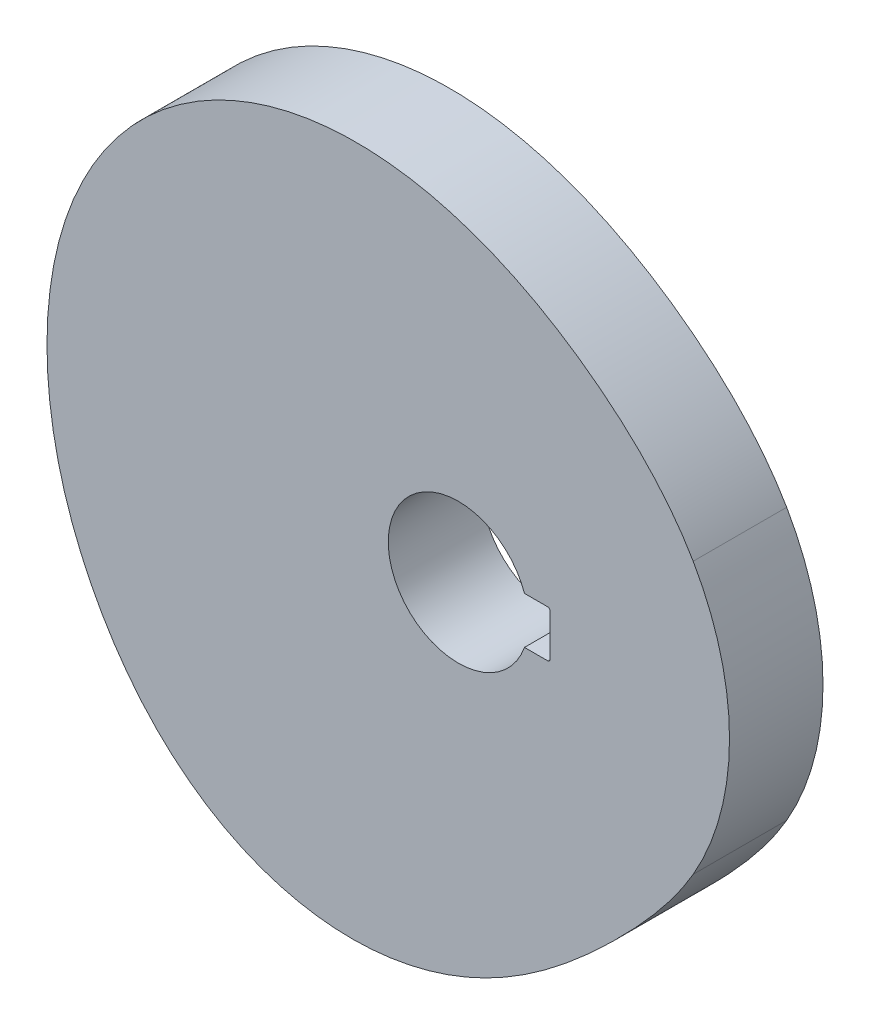
SolidWorks part; units mm, degrees
material "Plain Carbon Steel"
ref_plane "Front Plane" through (0, 0, 0) normal (0, 0, 1) x (1, 0, 0)
ref_plane "Top Plane" through (0, 0, 0) normal (0, 1, 0) x (1, 0, 0)
ref_plane "Right Plane" through (0, 0, 0) normal (1, 0, 0) x (0, 0, -1)
sketch "Displacement Sketch" plane through (0, 0, 0) normal (0, 0, 1) x (1, 0, 0)
  line L0 (0, 15) -> (0, 0) construction
  line L1 (0, 0) -> (47.1239, 0) construction
  line L2 (3.927, 0) -> (3.927, 15) construction
  line L3 (23.5619, 0) -> (23.5619, 15) construction
  line L4 (27.4889, 0) -> (27.4889, 15) construction
  line L5 (43.1969, 0) -> (43.1969, 15) construction
  line L6 (47.1239, 0) -> (47.1239, 15) construction
  line L7 (0, 0) -> (3.927, 0)
  line L8 (27.4889, 15) -> (23.5619, 15)
  line L9 (43.1969, 0) -> (47.1239, 0)
  spline S0 degree 4 poles (1.962, -0.0967) (2.0251, -0.0879) (2.1497, -0.0715) (2.3802, -0.0441) (2.7786, -0.0172) (3.1491, -0.0023) (3.8234, 0.0011) (4.1519, -0.0013) (4.7825, 0.0037) (5.2973, 0.0292) (5.8993, 0.0828) (6.4992, 0.198) (7.1843, 0.4092) (7.8229, 0.6945) (8.5028, 1.0958) (9.2434, 1.664) (10.1514, 2.5325) (11.1276, 3.6845) (12.1583, 5.0983) (13.2223, 6.6951) (14.2666, 8.3049) (15.3308, 9.9017) (16.361, 11.3155) (17.3382, 12.4675) (18.2447, 13.336) (18.9876, 13.9042) (19.6636, 14.3055) (20.2354, 14.5584) (20.6913, 14.7109) (21.0546, 14.8041) (21.3223, 14.8591) (21.5625, 14.8998) (21.7937, 14.9296) (22.0274, 14.9566) (22.3642, 14.9781) (22.6856, 14.9963) (23.3417, 15.0013) (23.6628, 14.9989) (24.3418, 15.0023) (24.7635, 15.0193) (25.1747, 15.049) (25.3985, 15.0791) (25.5259, 15.0967) knots 0 0 0 0 0 0.008159 0.016318 0.032637 0.048955 0.065274 0.0892 0.101163 0.113126 0.142767 0.163984 0.185201 0.206418 0.236195 0.268021 0.309045 0.372696 0.436348 0.5 0.563652 0.627304 0.690955 0.731979 0.763805 0.793582 0.814799 0.836016 0.846625 0.857233 0.864643 0.872053 0.879463 0.886874 0.898837 0.9108 0.934726 0.951045 0.967363 0.983682 1 1 1 1 1 construction
  spline S1 degree 4 poles (3.927, 0) (4.0838, 0) (4.3123, 0) (4.7825, 0.0037) (5.2973, 0.0292) (5.8993, 0.0828) (6.4992, 0.198) (7.1843, 0.4092) (7.8229, 0.6945) (8.5028, 1.0958) (9.2434, 1.664) (10.1514, 2.5325) (11.1276, 3.6845) (12.1583, 5.0983) (13.2223, 6.6951) (14.2666, 8.3049) (15.3308, 9.9017) (16.361, 11.3155) (17.3382, 12.4675) (18.2447, 13.336) (18.9876, 13.9042) (19.6636, 14.3055) (20.2354, 14.5584) (20.6913, 14.7109) (21.0546, 14.8041) (21.3223, 14.8591) (21.5625, 14.8998) (21.7937, 14.9296) (22.0274, 14.9566) (22.3642, 14.9781) (22.6856, 14.9963) (23.1748, 15) (23.4052, 15) (23.5619, 15) knots 0.065274 0.065274 0.065274 0.065274 0.065274 0.0892 0.101163 0.113126 0.142767 0.163984 0.185201 0.206418 0.236195 0.268021 0.309045 0.372696 0.436348 0.5 0.563652 0.627304 0.690955 0.731979 0.763805 0.793582 0.814799 0.836016 0.846625 0.857233 0.864643 0.872053 0.879463 0.886874 0.898837 0.9108 0.934726 0.934726 0.934726 0.934726 0.934726
  spline S2 degree 4 poles (25.917, 15.0967) (25.9672, 15.0879) (26.0664, 15.0716) (26.2503, 15.0442) (26.5692, 15.0173) (26.8684, 15.0023) (27.398, 14.9989) (27.6696, 15.0012) (28.1638, 14.9965) (28.4688, 14.9775) (28.7956, 14.949) (29.0691, 14.9044) (29.3652, 14.8416) (29.6303, 14.7623) (29.8895, 14.6683) (30.1363, 14.5572) (30.3781, 14.4298) (30.708, 14.2278) (31.1287, 13.9151) (31.7056, 13.3799) (32.4321, 12.5171) (33.1948, 11.3999) (33.9837, 10.0588) (34.759, 8.6207) (35.5133, 7.1717) (36.2737, 5.7258) (37.0683, 4.2981) (37.8437, 3.0586) (38.5964, 2.0494) (39.2866, 1.3197) (39.8479, 0.8516) (40.4053, 0.501) (40.8925, 0.2823) (41.3433, 0.149) (41.8164, 0.0573) (42.2412, 0.0166) (42.6103, 0.0017) (43.0977, -0.0005) (43.3551, 0.0006) (43.8251, -0.0023) (44.1115, -0.0173) (44.4386, -0.0442) (44.6184, -0.0716) (44.7185, -0.0879) (44.7693, -0.0967) knots 0 0 0 0 0 0.007472 0.014944 0.029888 0.044832 0.059777 0.081272 0.09202 0.102768 0.114604 0.126441 0.136767 0.147094 0.15742 0.167746 0.178072 0.188398 0.21612 0.247099 0.297177 0.359134 0.421092 0.48305 0.545008 0.606966 0.668924 0.730882 0.766656 0.797635 0.820922 0.841574 0.866069 0.878735 0.891402 0.915813 0.928018 0.940223 0.955168 0.970112 0.985056 0.992528 1 1 1 1 1 construction
  spline S3 degree 4 poles (27.4889, 15) (27.6137, 15) (27.7971, 15) (28.1638, 14.9965) (28.4688, 14.9775) (28.7956, 14.949) (29.0691, 14.9044) (29.3652, 14.8416) (29.6303, 14.7623) (29.8895, 14.6683) (30.1363, 14.5572) (30.3781, 14.4298) (30.708, 14.2278) (31.1287, 13.9151) (31.7056, 13.3799) (32.4321, 12.5171) (33.1948, 11.3999) (33.9837, 10.0588) (34.759, 8.6207) (35.5133, 7.1717) (36.2737, 5.7258) (37.0683, 4.2981) (37.8437, 3.0586) (38.5964, 2.0494) (39.2866, 1.3197) (39.8479, 0.8516) (40.4053, 0.501) (40.8925, 0.2823) (41.3433, 0.149) (41.8164, 0.0573) (42.2412, 0.0166) (42.6103, 0.0017) (42.9834, 0) (43.1261, 0) (43.1969, 0) knots 0.059777 0.059777 0.059777 0.059777 0.059777 0.081272 0.09202 0.102768 0.114604 0.126441 0.136767 0.147094 0.15742 0.167746 0.178072 0.188398 0.21612 0.247099 0.297177 0.359134 0.421092 0.48305 0.545008 0.606966 0.668924 0.730882 0.766656 0.797635 0.820922 0.841574 0.866069 0.878735 0.891402 0.915813 0.928018 0.940223 0.940223 0.940223 0.940223 0.940223
  point P2 (0, 0)
  point P17 (0, 0)
  dimension "D1" = 15
  dimension "D2" = 47.1239
  dimension "D3" = 3.927
  dimension "D4" = 19.635
  dimension "D5" = 3.927
  dimension "D6" = 15.708
  dimension "D7" = 3.927
sketch "Velocity Sketch" plane through (0, 0, 0) normal (0, 0, 1) x (1, 0, 0)
  line L0 (0, -15) -> (0, -65) construction
  line L1 (0, -40) -> (47.1239, -40) construction
  line L2 (3.927, -15) -> (3.927, -65) construction
  line L3 (23.5619, -15) -> (23.5619, -65) construction
  line L4 (27.4889, -15) -> (27.4889, -65) construction
  line L5 (43.1969, -15) -> (43.1969, -65) construction
  line L6 (47.1239, -15) -> (47.1239, -65) construction
  line L7 (0, -40) -> (3.927, -40)
  line L8 (23.5619, -40) -> (27.4889, -40)
  line L9 (43.1969, -40) -> (47.1239, -40)
  spline S0 degree 4 number of poles 82 (1.9635, -38.9057) -> (25.5254, -38.9057) construction
  spline S1 degree 4 poles (3.927, -40) (3.9591, -40) (4.0069, -39.9984) (4.0914, -39.9931) (4.2047, -39.9788) (4.3113, -39.9585) (4.4273, -39.9287) (4.5497, -39.8882) (4.6855, -39.8341) (4.8338, -39.7637) (5.0005, -39.6692) (5.2228, -39.5203) (5.4703, -39.3234) (5.7369, -39.0742) (6.0182, -38.7713) (6.2635, -38.4767) (6.4789, -38.1966) (6.7119, -37.8755) (6.9601, -37.5119) (7.2378, -37.08) (7.6188, -36.4531) (8.0578, -35.69) (8.695, -34.5334) (9.3923, -33.2428) (10.1106, -31.9631) (10.8521, -30.798) (11.4447, -29.9912) (12.0701, -29.306) (12.6823, -28.8165) (13.3594, -28.5265) (13.9982, -28.5224) (14.4931, -28.6816) (14.9938, -28.9673) (15.4821, -29.3759) (16.0352, -29.9801) (16.6301, -30.7877) (17.3726, -31.9534) (18.0917, -33.2337) (18.7893, -34.5249) (19.4267, -35.6821) (19.8657, -36.4456) (20.2468, -37.073) (20.5641, -37.567) (20.8732, -38.0148) (21.1744, -38.4151) (21.4671, -38.7672) (21.7491, -39.0713) (22.0564, -39.3589) (22.3514, -39.5861) (22.6045, -39.7396) (22.8026, -39.8338) (22.9386, -39.888) (23.0611, -39.9286) (23.1771, -39.9584) (23.2842, -39.9788) (23.3789, -39.9907) (23.4581, -39.9971) (23.5136, -39.9995) (23.5459, -40) (23.5619, -40) knots 0.064432 0.064432 0.064432 0.064432 0.064432 0.068544 0.0706 0.072656 0.076768 0.08088 0.083926 0.086973 0.093066 0.099159 0.105252 0.116762 0.128271 0.13978 0.15129 0.159464 0.167638 0.183987 0.200336 0.216684 0.249382 0.282079 0.347474 0.380171 0.412868 0.435887 0.458906 0.483278 0.499726 0.516191 0.528398 0.540605 0.563699 0.586794 0.619507 0.652221 0.717647 0.750361 0.783074 0.799431 0.815787 0.832144 0.8485 0.860048 0.871595 0.883143 0.89469 0.906897 0.913 0.916052 0.919104 0.92322 0.927336 0.929394 0.931452 0.93351 0.935568 0.935568 0.935568 0.935568 0.935568
  spline S2 degree 4 number of poles 99 (25.9181, -41.3678) -> (44.7677, -41.3678) construction
  spline S3 degree 4 number of poles 73 (27.4889, -40) -> (43.1969, -40)
  point P15 (23.5619, -40)
  point P27 (43.1969, -40)
  point P28 (3.927, -40)
  point P35 (27.4889, -40)
  dimension "D1" = 50
  dimension "D2" = 15
  dimension "D3" = 47.1239
sketch "Acceleration Sketch" plane through (0, 0, 0) normal (0, 0, 1) x (1, 0, 0)
  line L0 (0, -80) -> (0, -130) construction
  line L1 (0, -15) -> (0, -65) construction
  line L2 (3.927, -80) -> (3.927, -130) construction
  line L3 (23.5619, -80) -> (23.5619, -130) construction
  line L4 (27.4889, -80) -> (27.4889, -130) construction
  line L5 (43.1969, -80) -> (43.1969, -130) construction
  line L6 (47.1239, -80) -> (47.1239, -130) construction
  line L7 (0, -105) -> (47.1239, -105) construction
  spline S0 degree 4 number of poles 85 (2.572, -110.7775) -> (24.917, -99.2225) construction
  spline S1 degree 4 number of poles 69 (3.927, -105) -> (23.5619, -105)
  spline S2 degree 4 number of poles 85 (26.4484, -96.3102) -> (44.2375, -113.6898) construction
  spline S3 degree 4 number of poles 77 (27.4889, -105) -> (43.1969, -105)
  point P18 (23.8027, -105)
  point P26 (0, 0)
  point P30 (3.927, -105)
  point P31 (22.5917, -105)
  point P32 (0, 0)
  point P33 (0, 0)
  point P34 (0, 0)
  point P35 (0, 0)
  point P38 (96.3313, -100.333)
  point P40 (0, 0)
  point P41 (0, 0)
  point P42 (81.6814, -111.0248)
  point P43 (0, 0)
  point P44 (0, 0)
  point P45 (0, 0)
  point P46 (81.6814, -109.963)
  point P47 (81.6814, -105)
  point P48 (60.6009, -105)
  point P49 (0, 0)
  point P50 (0, 0)
  dimension "D1" = 15
sketch "Cam Profile Sketch" plane through (0, 0, 0) normal (0, 0, 1) x (1, 0, 0)
  line L0 (-49, 0) -> (-93, 0) construction
  line L1 (-49, 0) -> (-23.8853, 14.5) construction
  line L3 (-49, 0) -> (-87.1051, -22) construction
  line L4 (-23.8853, -14.5) -> (-49, 0) construction
  circle A1 centre (-49, 0) radius 29 construction
  arc A2 (-93, 0) -> (-87.1051, -22) centre (-49, 0) ccw
  arc A3 (-23.8853, -14.5) -> (-23.8853, 14.5) centre (-49, 0) ccw
  spline S0 degree 4 number of poles 84 (-21.0816, 7.4807) -> (-91.9863, -9.6611) construction
  spline S1 degree 4 poles (-23.8853, 14.5) (-23.9328, 14.5824) (-24.0277, 14.7445) (-24.2319, 15.0878) (-24.4645, 15.4634) (-24.7034, 15.8366) (-24.9512, 16.2123) (-25.2035, 16.5831) (-25.4607, 16.9499) (-25.7512, 17.3524) (-26.2677, 18.0453) (-27.1324, 19.1368) (-28.4165, 20.6093) (-30.1456, 22.3683) (-31.9522, 24.0003) (-33.682, 25.4157) (-35.2829, 26.6203) (-36.7346, 27.637) (-38.214, 28.6) (-39.7256, 29.5117) (-41.2684, 30.3695) (-43.2348, 31.3707) (-45.6528, 32.452) (-48.5535, 33.523) (-51.6032, 34.3581) (-54.3423, 34.8797) (-57.1097, 35.211) (-59.8951, 35.3457) (-63.056, 35.2217) (-66.5557, 34.7132) (-69.9807, 33.8313) (-73.2889, 32.5802) (-76.4387, 30.9712) (-79.4088, 29.0105) (-82.1582, 26.7166) (-84.6496, 24.1145) (-86.8505, 21.2354) (-88.7264, 18.1351) (-90.2072, 14.9786) (-91.2012, 12.1859) (-91.847, 9.8314) (-92.2209, 8.1094) (-92.439, 6.9089) (-92.5993, 5.859) (-92.7156, 4.9622) (-92.7998, 4.1755) (-92.8596, 3.4999) (-92.9013, 2.9365) (-92.9298, 2.4854) (-92.9534, 2.0327) (-92.9723, 1.5812) (-92.9864, 1.1389) (-92.9957, 0.6708) (-92.9992, 0.2901) (-93, 0.0959) (-93, 0) knots 0.066188 0.066188 0.066188 0.066188 0.066188 0.070099 0.07401 0.07792 0.081831 0.085742 0.089653 0.093564 0.097475 0.103059 0.11981 0.142146 0.165611 0.189076 0.204719 0.220116 0.235513 0.25091 0.266306 0.281703 0.2971 0.327893 0.358686 0.38948 0.407291 0.425102 0.455895 0.486688 0.517482 0.548275 0.579069 0.609862 0.640655 0.672207 0.70376 0.735312 0.766864 0.798416 0.82521 0.838607 0.852004 0.859892 0.86778 0.875668 0.883556 0.8875 0.891444 0.895388 0.899332 0.903276 0.90722 0.911164 0.915108 0.915108 0.915108 0.915108 0.915108
  spline S2 degree 4 number of poles 81 (-21.5114, -8.9316) -> (-90.4641, -14.9011) construction
  spline S3 degree 4 poles (-23.8853, -14.5) (-23.9228, -14.565) (-23.9986, -14.695) (-24.1533, -14.9565) (-24.3405, -15.2639) (-24.5245, -15.5577) (-24.7154, -15.8558) (-24.9096, -16.152) (-25.204, -16.5908) (-25.5555, -17.0963) (-26.07, -17.8075) (-26.6555, -18.5744) (-27.2016, -19.2598) (-27.9845, -20.2063) (-28.905, -21.2718) (-29.9727, -22.445) (-31.1919, -23.7204) (-32.3132, -24.8484) (-33.3264, -25.8344) (-34.356, -26.8033) (-35.4027, -27.7536) (-36.4677, -28.6835) (-37.5521, -29.5906) (-38.6574, -30.4723) (-40.0665, -31.5389) (-41.5142, -32.5534) (-43.2999, -33.6987) (-45.4952, -34.9391) (-47.7646, -36.0414) (-50.4458, -37.085) (-53.2075, -37.8928) (-55.9852, -38.4418) (-58.8021, -38.7298) (-61.634, -38.7457) (-64.4538, -38.4832) (-67.3037, -37.9274) (-69.7768, -37.1729) (-71.8775, -36.3239) (-73.6249, -35.4667) (-75.324, -34.5176) (-76.9536, -33.4513) (-78.5066, -32.2766) (-79.9784, -31.0034) (-80.9649, -30.0639) (-81.7785, -29.2267) (-82.4351, -28.5089) (-82.9475, -27.9232) (-83.4441, -27.3299) (-83.925, -26.73) (-84.391, -26.1233) (-84.8413, -25.5121) (-85.2807, -24.8903) (-85.7062, -24.2635) (-86.123, -23.6232) (-86.4733, -23.0634) (-86.7658, -22.58) (-86.9827, -22.2109) (-87.0648, -22.0699) (-87.1051, -22) knots 0.065589 0.065589 0.065589 0.065589 0.065589 0.069408 0.073227 0.077046 0.080865 0.084684 0.088503 0.092322 0.103716 0.111291 0.126441 0.134017 0.141592 0.16438 0.187294 0.202569 0.217845 0.233121 0.248396 0.263672 0.278948 0.294223 0.309499 0.324775 0.355326 0.370602 0.401153 0.433708 0.464259 0.49481 0.525362 0.555913 0.586464 0.617016 0.647567 0.6812 0.698016 0.714832 0.731649 0.765281 0.782098 0.798914 0.81573 0.824138 0.832546 0.840955 0.849363 0.857574 0.865785 0.873997 0.882208 0.890419 0.898631 0.906842 0.910948 0.915054 0.915054 0.915054 0.915054 0.915054
  dimension "D2" = 29
  dimension "D1" = 49
  dimension "D3" = 44
  dimension "D4" = 30
  dimension "D6" = 30
  dimension "D7" = 30
  dimension "D8" = 180
extrude "Boss-Extrude1" add sketch "Cam Profile Sketch" along normal mid plane 10 contours S1 A2 S3 A3
sketch "Sketch2" plane through (0, 0, 0) normal (0, 0, 1) x (1, 0, 0)
  circle A0 centre (-49, 0) radius 7.5
  dimension "D1" = 15
extrude "Cut-Extrude2" cut sketch "Sketch2" against normal up to next and the other way up to next
sketch "Sketch3" plane through (0, 0, 0) normal (0, 0, 1) x (1, 0, 0)
  line L0 (-49, 0) -> (-41.5, 0) construction
  line L2 (-41.9289, 2.5) -> (-39.2, 2.5)
  line L3 (-41.9289, 2.5) -> (-41.9289, -2.5)
  line L4 (-41.9289, -2.5) -> (-39.2, -2.5)
  line L5 (-39.2, 2.5) -> (-39.2, -2.5)
  circle A0 centre (-49, 0) radius 7.5 construction
  point P9 (0, 0)
  dimension "D1" = 5
  dimension "D2" = 2.3
extrude "Cut-Extrude3" cut sketch "Sketch3" against normal up to next and the other way up to next
fillet "Fillet1" radius 0.25 2 edges at (-39.2, -2.5, 0) (-39.2, 2.5, 0)
sketch "Sketch6" plane through (0, 0, 0) normal (0, 0, 1) x (1, 0, 0)
  arc A4 (-14.359, -20) -> (-14.359, 20) centre (-49, 0) ccw
  arc A6 (-14.359, -20) -> (-14.359, 20) centre (-49, 0) ccw construction
  spline S2 degree 3 poles (-104, 0) (-104, -9.7106) (-101.4867, -19.0904) (-96.6314, -27.5) knots 0 0 0 0 1 1 1 1 weights 1 0.977284 0.977284 1
  spline S3 degree 3 poles (-104, 0) (-104, -9.7106) (-101.4867, -19.0904) (-96.6314, -27.5) knots 0 0 0 0 1 1 1 1 weights 1 0.977284 0.977284 1
  spline S4 degree 3 poles (-2121.3509, -2107.8884) (-90.1041, -268.0393) (38.8532, -41.6264) (-20.5996, 28.4116) (-22.4507, 30.2678) (-24.9339, 32.4444) (-25.4387, 32.8721) (-26.4578, 33.7074) (-26.9729, 34.1158) (-28.5344, 35.3143) (-29.5968, 36.0777) (-32.8466, 38.2639) (-35.096, 39.5839) (-38.6055, 41.3389) (-39.7981, 41.886) (-41.6241, 42.6453) (-42.2401, 42.8885) (-43.4792, 43.3515) (-44.1013, 43.5708) (-47.2243, 44.6062) (-49.7632, 45.239) (-53.6363, 45.8756) (-54.9381, 46.0356) (-57.5645, 46.2456) (-58.895, 46.2951) (-62.8479, 46.27) (-65.4489, 46.0259) (-69.2986, 45.3166) (-70.5732, 45.0228) (-72.4716, 44.493) (-73.1022, 44.3015) (-74.3588, 43.8881) (-74.9855, 43.6658) (-78.0732, 42.4898) (-80.4238, 41.3359) (-83.7745, 39.2932) (-84.8621, 38.5601) (-86.9774, 36.9869) (-88.0088, 36.143) (-90.9518, 33.4994) (-92.7313, 31.5775) (-95.1366, 28.464) (-95.8941, 27.3876) (-96.9631, 25.7141) (-97.3081, 25.1465) (-97.9694, 24.0026) (-98.2864, 23.425) (-99.8056, 20.5097) (-100.8105, 18.0901) (-101.8163, 14.9617) (-102.0048, 14.3308) (-102.3568, 13.0586) (-102.5205, 12.4162) (-102.9719, 10.4812) (-103.2193, 9.185) (-136.6485, -212.174) (1276.4183, -601.8103) (-3010.0616, -323.1715) knots -2.072484 -2.072484 -2.072484 -2.072484 0.0625 0.0625 0.125 0.125 0.140625 0.140625 0.15625 0.15625 0.1875 0.1875 0.25 0.25 0.28125 0.28125 0.296875 0.296875 0.3125 0.3125 0.375 0.375 0.40625 0.40625 0.4375 0.4375 0.5 0.5 0.53125 0.53125 0.546875 0.546875 0.5625 0.5625 0.625 0.625 0.65625 0.65625 0.6875 0.6875 0.75 0.75 0.78125 0.78125 0.796875 0.796875 0.8125 0.8125 0.875 0.875 0.890625 0.890625 0.90625 0.90625 0.9375 0.9375 6.218529 6.218529 6.218529 6.218529 only from (-14.359, 20) to (-104, 0)
  spline S5 degree 3 poles (-2669.4706, -1511.9471) (347.9627, 724.0401) (-201.4987, 75.5733) (-88.246, -38.3286) (-87.4685, -39.057) (-85.8573, -40.4573) (-85.0312, -41.1228) (-82.492, -43.0154) (-80.7182, -44.1392) (-77.9326, -45.6129) (-76.9833, -46.0686) (-75.5269, -46.6973) (-75.036, -46.8976) (-74.0433, -47.2796) (-73.5402, -47.4616) (-71.0112, -48.3187) (-68.96, -48.8314) (-64.8037, -49.5242) (-62.6986, -49.7043) (-60.0329, -49.7174) (-59.4973, -49.7092) (-58.4318, -49.6719) (-57.9009, -49.6427) (-56.3137, -49.5242) (-55.2629, -49.404) (-52.1315, -48.9244) (-50.0719, -48.446) (-47.0233, -47.4984) (-46.0126, -47.1432) (-44.0327, -46.3685) (-43.06, -45.9479) (-40.1903, -44.5927) (-38.3418, -43.5645) (-35.6544, -41.8576) (-34.7712, -41.2599) (-33.0389, -40.0196) (-32.1924, -39.3789) (-29.7036, -37.4036) (-28.1117, -36.0161) (-25.027, -33.1371) (-23.5326, -31.6474) (-20.6447, -28.562) (-19.2514, -26.9647) (30.4783, 36.9799) (-58.8139, 192.9555) (-2354.1483, 1850.1458) knots -4.584283 -4.584283 -4.584283 -4.584283 0.125 0.125 0.15625 0.15625 0.1875 0.1875 0.25 0.25 0.28125 0.28125 0.296875 0.296875 0.3125 0.3125 0.375 0.375 0.4375 0.4375 0.453125 0.453125 0.46875 0.46875 0.5 0.5 0.5625 0.5625 0.59375 0.59375 0.625 0.625 0.6875 0.6875 0.71875 0.71875 0.75 0.75 0.8125 0.8125 0.875 0.875 0.9375 0.9375 3.249827 3.249827 3.249827 3.249827 only from (-96.6314, -27.5) to (-14.359, -20)
  spline S6 degree 3 poles (-14.359, 20) (-15.6869, 22.2999) (-17.2178, 24.4276) (-20.5996, 28.4116) (-22.4507, 30.2678) (-24.9339, 32.4444) (-25.4387, 32.8721) (-26.4578, 33.7074) (-26.9729, 34.1158) (-28.5344, 35.3143) (-29.5968, 36.0777) (-32.8466, 38.2639) (-35.096, 39.5839) (-38.6055, 41.3389) (-39.7981, 41.886) (-41.6241, 42.6453) (-42.2401, 42.8885) (-43.4792, 43.3515) (-44.1013, 43.5708) (-47.2243, 44.6062) (-49.7632, 45.239) (-53.6363, 45.8756) (-54.9381, 46.0356) (-57.5645, 46.2456) (-58.895, 46.2951) (-62.8479, 46.27) (-65.4489, 46.0259) (-69.2986, 45.3166) (-70.5732, 45.0228) (-72.4716, 44.493) (-73.1022, 44.3015) (-74.3588, 43.8881) (-74.9855, 43.6658) (-78.0732, 42.4898) (-80.4238, 41.3359) (-83.7745, 39.2932) (-84.8621, 38.5601) (-86.9774, 36.9869) (-88.0088, 36.143) (-90.9518, 33.4994) (-92.7313, 31.5775) (-95.1366, 28.464) (-95.8941, 27.3876) (-96.9631, 25.7141) (-97.3081, 25.1465) (-97.9694, 24.0026) (-98.2864, 23.425) (-99.8056, 20.5097) (-100.8105, 18.0901) (-101.8163, 14.9617) (-102.0048, 14.3308) (-102.3568, 13.0586) (-102.5205, 12.4162) (-102.9719, 10.4812) (-103.2193, 9.185) (-103.8093, 5.2785) (-104, 2.6504) (-104, 0) knots 0 0 0 0 0.0625 0.0625 0.125 0.125 0.140625 0.140625 0.15625 0.15625 0.1875 0.1875 0.25 0.25 0.28125 0.28125 0.296875 0.296875 0.3125 0.3125 0.375 0.375 0.40625 0.40625 0.4375 0.4375 0.5 0.5 0.53125 0.53125 0.546875 0.546875 0.5625 0.5625 0.625 0.625 0.65625 0.65625 0.6875 0.6875 0.75 0.75 0.78125 0.78125 0.796875 0.796875 0.8125 0.8125 0.875 0.875 0.890625 0.890625 0.90625 0.90625 0.9375 0.9375 1 1 1 1 construction
  spline S7 degree 3 poles (-96.6314, -27.5) (-94.4988, -31.1938) (-91.9789, -34.5743) (-88.246, -38.3286) (-87.4685, -39.057) (-85.8573, -40.4573) (-85.0312, -41.1228) (-82.492, -43.0154) (-80.7182, -44.1392) (-77.9326, -45.6129) (-76.9833, -46.0686) (-75.5269, -46.6973) (-75.036, -46.8976) (-74.0433, -47.2796) (-73.5402, -47.4616) (-71.0112, -48.3187) (-68.96, -48.8314) (-64.8037, -49.5242) (-62.6986, -49.7043) (-60.0329, -49.7174) (-59.4973, -49.7092) (-58.4318, -49.6719) (-57.9009, -49.6427) (-56.3137, -49.5242) (-55.2629, -49.404) (-52.1315, -48.9244) (-50.0719, -48.446) (-47.0233, -47.4984) (-46.0126, -47.1432) (-44.0327, -46.3685) (-43.06, -45.9479) (-40.1903, -44.5927) (-38.3418, -43.5645) (-35.6544, -41.8576) (-34.7712, -41.2599) (-33.0389, -40.0196) (-32.1924, -39.3789) (-29.7036, -37.4036) (-28.1117, -36.0161) (-25.027, -33.1371) (-23.5326, -31.6474) (-20.6447, -28.562) (-19.2514, -26.9647) (-16.6339, -23.5989) (-15.4257, -21.8476) (-14.359, -20) knots 0 0 0 0 0.125 0.125 0.15625 0.15625 0.1875 0.1875 0.25 0.25 0.28125 0.28125 0.296875 0.296875 0.3125 0.3125 0.375 0.375 0.4375 0.4375 0.453125 0.453125 0.46875 0.46875 0.5 0.5 0.5625 0.5625 0.59375 0.59375 0.625 0.625 0.6875 0.6875 0.71875 0.71875 0.75 0.75 0.8125 0.8125 0.875 0.875 0.9375 0.9375 1 1 1 1 construction
  point P0 (0, 0)
  dimension "D1" = 11
sketch3d "3DSketch1"
  arc A0 (-23.8853, 14.5, 0) -> (-23.8853, -14.5, 0) centre (-49, 0, 0) ccw
  arc A1 (-23.8853, 14.5, 0) -> (-23.8853, -14.5, 0) centre (-49, 0, 0) ccw
  arc A2 (-87.1051, -22, 0) -> (-93, 0, 0) centre (-49, 0, 0) ccw
  arc A3 (-87.1051, -22, 0) -> (-93, 0, 0) centre (-49, 0, 0) ccw
  spline S0 degree 4 poles (-586.6738, 843.9168, 0) (-72.8081, -46.4545, 0) (-88.829, -18.945, 0) (-87.4681, -21.4195, 0) (-86.4733, -23.0634, 0) (-86.123, -23.6232, 0) (-85.7062, -24.2635, 0) (-85.2807, -24.8903, 0) (-84.8413, -25.5121, 0) (-84.391, -26.1233, 0) (-83.925, -26.73, 0) (-83.4441, -27.3299, 0) (-82.9475, -27.9232, 0) (-82.4351, -28.5089, 0) (-81.7785, -29.2267, 0) (-80.9649, -30.0639, 0) (-79.9784, -31.0034, 0) (-78.5066, -32.2766, 0) (-76.9536, -33.4513, 0) (-75.324, -34.5176, 0) (-73.6249, -35.4667, 0) (-71.8775, -36.3239, 0) (-69.7768, -37.1729, 0) (-67.3037, -37.9274, 0) (-64.4538, -38.4832, 0) (-61.634, -38.7457, 0) (-58.8021, -38.7298, 0) (-55.9852, -38.4418, 0) (-53.2075, -37.8928, 0) (-50.4458, -37.085, 0) (-47.7646, -36.0414, 0) (-45.4952, -34.9391, 0) (-43.2999, -33.6987, 0) (-41.5142, -32.5534, 0) (-40.0665, -31.5389, 0) (-38.6574, -30.4723, 0) (-37.5521, -29.5906, 0) (-36.4677, -28.6835, 0) (-35.4027, -27.7536, 0) (-34.356, -26.8033, 0) (-33.3264, -25.8344, 0) (-32.3132, -24.8484, 0) (-31.1919, -23.7204, 0) (-29.9727, -22.445, 0) (-28.905, -21.2718, 0) (-27.9845, -20.2063, 0) (-27.2016, -19.2598, 0) (-26.6555, -18.5744, 0) (-26.07, -17.8075, 0) (-25.5555, -17.0963, 0) (-25.204, -16.5908, 0) (-24.9096, -16.152, 0) (-24.7154, -15.8558, 0) (-24.5245, -15.5577, 0) (-24.3405, -15.2639, 0) (-23.4912, -13.869, 0) (-22.2224, -11.5409, 0) (-38.2993, -39.0434, 0) (475.6566, 851.7024, 0) knots 0.006452 0.006452 0.006452 0.006452 0.006452 0.069695 0.0738 0.082012 0.090223 0.098435 0.106646 0.114857 0.123069 0.13128 0.139688 0.148096 0.156504 0.164913 0.181729 0.198545 0.215361 0.248994 0.26581 0.282627 0.299443 0.333075 0.363627 0.394178 0.42473 0.455281 0.485832 0.516384 0.546935 0.57949 0.610041 0.625317 0.655868 0.671144 0.686419 0.701695 0.716971 0.732246 0.747522 0.762798 0.778073 0.793349 0.816263 0.839051 0.846626 0.854201 0.869352 0.876927 0.888321 0.89214 0.895959 0.899778 0.903597 0.907416 0.911235 0.969085 0.969085 0.969085 0.969085 0.969085 only from (-87.1051, -22, 0) to (-23.8853, -14.5, 0)
  spline S1 degree 4 poles (-87.1051, -22, 0) (-87.0648, -22.0699, 0) (-86.9827, -22.2109, 0) (-86.7658, -22.58, 0) (-86.4733, -23.0634, 0) (-86.123, -23.6232, 0) (-85.7062, -24.2635, 0) (-85.2807, -24.8903, 0) (-84.8413, -25.5121, 0) (-84.391, -26.1233, 0) (-83.925, -26.73, 0) (-83.4441, -27.3299, 0) (-82.9475, -27.9232, 0) (-82.4351, -28.5089, 0) (-81.7785, -29.2267, 0) (-80.9649, -30.0639, 0) (-79.9784, -31.0034, 0) (-78.5066, -32.2766, 0) (-76.9536, -33.4513, 0) (-75.324, -34.5176, 0) (-73.6249, -35.4667, 0) (-71.8775, -36.3239, 0) (-69.7768, -37.1729, 0) (-67.3037, -37.9274, 0) (-64.4538, -38.4832, 0) (-61.634, -38.7457, 0) (-58.8021, -38.7298, 0) (-55.9852, -38.4418, 0) (-53.2075, -37.8928, 0) (-50.4458, -37.085, 0) (-47.7646, -36.0414, 0) (-45.4952, -34.9391, 0) (-43.2999, -33.6987, 0) (-41.5142, -32.5534, 0) (-40.0665, -31.5389, 0) (-38.6574, -30.4723, 0) (-37.5521, -29.5906, 0) (-36.4677, -28.6835, 0) (-35.4027, -27.7536, 0) (-34.356, -26.8033, 0) (-33.3264, -25.8344, 0) (-32.3132, -24.8484, 0) (-31.1919, -23.7204, 0) (-29.9727, -22.445, 0) (-28.905, -21.2718, 0) (-27.9845, -20.2063, 0) (-27.2016, -19.2598, 0) (-26.6555, -18.5744, 0) (-26.07, -17.8075, 0) (-25.5555, -17.0963, 0) (-25.204, -16.5908, 0) (-24.9096, -16.152, 0) (-24.7154, -15.8558, 0) (-24.5245, -15.5577, 0) (-24.3405, -15.2639, 0) (-24.1533, -14.9565, 0) (-23.9986, -14.695, 0) (-23.9228, -14.565, 0) (-23.8853, -14.5, 0) knots 0.065589 0.065589 0.065589 0.065589 0.065589 0.069695 0.0738 0.082012 0.090223 0.098435 0.106646 0.114857 0.123069 0.13128 0.139688 0.148096 0.156504 0.164913 0.181729 0.198545 0.215361 0.248994 0.26581 0.282627 0.299443 0.333075 0.363627 0.394178 0.42473 0.455281 0.485832 0.516384 0.546935 0.57949 0.610041 0.625317 0.655868 0.671144 0.686419 0.701695 0.716971 0.732246 0.747522 0.762798 0.778073 0.793349 0.816263 0.839051 0.846626 0.854201 0.869352 0.876927 0.888321 0.89214 0.895959 0.899778 0.903597 0.907416 0.911235 0.915054 0.915054 0.915054 0.915054 0.915054
  spline S2 degree 4 poles (-92.5694, -999.9322, 0) (-92.7955, 28.9968, 0) (-92.9561, -3.8662, 0) (-93.0282, -0.9534, 0) (-92.9864, 1.1389, 0) (-92.9723, 1.5812, 0) (-92.9534, 2.0327, 0) (-92.9298, 2.4854, 0) (-92.9013, 2.9365, 0) (-92.8596, 3.4999, 0) (-92.7998, 4.1755, 0) (-92.7156, 4.9622, 0) (-92.5993, 5.859, 0) (-92.439, 6.9089, 0) (-92.2209, 8.1094, 0) (-91.847, 9.8314, 0) (-91.2012, 12.1859, 0) (-90.2072, 14.9786, 0) (-88.7264, 18.1351, 0) (-86.8505, 21.2354, 0) (-84.6496, 24.1145, 0) (-82.1582, 26.7166, 0) (-79.4088, 29.0105, 0) (-76.4387, 30.9712, 0) (-73.2889, 32.5802, 0) (-69.9807, 33.8313, 0) (-66.5557, 34.7132, 0) (-63.056, 35.2217, 0) (-59.8951, 35.3457, 0) (-57.1097, 35.211, 0) (-54.3423, 34.8797, 0) (-51.6032, 34.3581, 0) (-48.5535, 33.523, 0) (-45.6528, 32.452, 0) (-43.2348, 31.3707, 0) (-41.2684, 30.3695, 0) (-39.7256, 29.5117, 0) (-38.214, 28.6, 0) (-36.7346, 27.637, 0) (-35.2829, 26.6203, 0) (-33.682, 25.4157, 0) (-31.9522, 24.0003, 0) (-30.1456, 22.3683, 0) (-28.4165, 20.6093, 0) (-27.1324, 19.1368, 0) (-26.2677, 18.0453, 0) (-25.7512, 17.3524, 0) (-25.4607, 16.9499, 0) (-25.2035, 16.5831, 0) (-24.9512, 16.2123, 0) (-24.7034, 15.8366, 0) (-24.4645, 15.4634, 0) (-23.5071, 13.9173, 0) (-21.8171, 10.8267, 0) (-40.1465, 42.1549, 0) (475.4469, -851.5211, 0) knots 0.011452 0.011452 0.011452 0.011452 0.011452 0.070132 0.074076 0.07802 0.081964 0.085908 0.089852 0.093796 0.09774 0.105628 0.113516 0.121404 0.129292 0.142689 0.156086 0.18288 0.214432 0.245984 0.277536 0.309089 0.340641 0.371434 0.402227 0.433021 0.463814 0.494608 0.525401 0.556194 0.574005 0.591816 0.62261 0.653403 0.684196 0.699593 0.71499 0.730386 0.745783 0.76118 0.776576 0.79222 0.815685 0.83915 0.861486 0.878237 0.883821 0.887732 0.891643 0.895554 0.899465 0.903376 0.907286 0.911197 0.963859 0.963859 0.963859 0.963859 0.963859 only from (-93, 0, 0) to (-23.8853, 14.5, 0)
  spline S3 degree 4 poles (-93, 0, 0) (-93, 0.0959, 0) (-92.9992, 0.2901, 0) (-92.9957, 0.6708, 0) (-92.9864, 1.1389, 0) (-92.9723, 1.5812, 0) (-92.9534, 2.0327, 0) (-92.9298, 2.4854, 0) (-92.9013, 2.9365, 0) (-92.8596, 3.4999, 0) (-92.7998, 4.1755, 0) (-92.7156, 4.9622, 0) (-92.5993, 5.859, 0) (-92.439, 6.9089, 0) (-92.2209, 8.1094, 0) (-91.847, 9.8314, 0) (-91.2012, 12.1859, 0) (-90.2072, 14.9786, 0) (-88.7264, 18.1351, 0) (-86.8505, 21.2354, 0) (-84.6496, 24.1145, 0) (-82.1582, 26.7166, 0) (-79.4088, 29.0105, 0) (-76.4387, 30.9712, 0) (-73.2889, 32.5802, 0) (-69.9807, 33.8313, 0) (-66.5557, 34.7132, 0) (-63.056, 35.2217, 0) (-59.8951, 35.3457, 0) (-57.1097, 35.211, 0) (-54.3423, 34.8797, 0) (-51.6032, 34.3581, 0) (-48.5535, 33.523, 0) (-45.6528, 32.452, 0) (-43.2348, 31.3707, 0) (-41.2684, 30.3695, 0) (-39.7256, 29.5117, 0) (-38.214, 28.6, 0) (-36.7346, 27.637, 0) (-35.2829, 26.6203, 0) (-33.682, 25.4157, 0) (-31.9522, 24.0003, 0) (-30.1456, 22.3683, 0) (-28.4165, 20.6093, 0) (-27.1324, 19.1368, 0) (-26.2677, 18.0453, 0) (-25.7512, 17.3524, 0) (-25.4607, 16.9499, 0) (-25.2035, 16.5831, 0) (-24.9512, 16.2123, 0) (-24.7034, 15.8366, 0) (-24.4645, 15.4634, 0) (-24.2319, 15.0878, 0) (-24.0277, 14.7445, 0) (-23.9328, 14.5824, 0) (-23.8853, 14.5, 0) knots 0.066188 0.066188 0.066188 0.066188 0.066188 0.070132 0.074076 0.07802 0.081964 0.085908 0.089852 0.093796 0.09774 0.105628 0.113516 0.121404 0.129292 0.142689 0.156086 0.18288 0.214432 0.245984 0.277536 0.309089 0.340641 0.371434 0.402227 0.433021 0.463814 0.494608 0.525401 0.556194 0.574005 0.591816 0.62261 0.653403 0.684196 0.699593 0.71499 0.730386 0.745783 0.76118 0.776576 0.79222 0.815685 0.83915 0.861486 0.878237 0.883821 0.887732 0.891643 0.895554 0.899465 0.903376 0.907286 0.911197 0.915108 0.915108 0.915108 0.915108 0.915108
  point P4 (-49, 0, -29)
  point P5 (-49, 0, -29)
  point P8 (-49, 0, -44)
  point P9 (-49, 0, -44)
sketch "Sketch7" plane through (0, 0, 0) normal (0, 0, 1) x (1, 0, 0)
  arc A0 (-14.359, -20) -> (-14.359, 20) centre (-49, 0) ccw construction
  arc A1 (-104, 0) -> (-96.6314, -27.5) centre (-49, 0) ccw construction
  arc A2 (-14.359, -20) -> (-14.359, 20) centre (-49, 0) ccw
  arc A3 (-104, 0) -> (-96.6314, -27.5) centre (-49, 0) ccw
  spline S0 degree 3 poles (-1044.4776, -346.2007) (120.609, 441.29) (-174.246, 48.1643) (-88.246, -38.3286) (-87.4685, -39.057) (-85.8573, -40.4573) (-85.0312, -41.1228) (-82.492, -43.0154) (-80.7182, -44.1392) (-77.9326, -45.6129) (-76.9833, -46.0686) (-75.5269, -46.6973) (-75.036, -46.8976) (-74.0433, -47.2796) (-73.5402, -47.4616) (-71.0112, -48.3187) (-68.96, -48.8314) (-64.8037, -49.5242) (-62.6986, -49.7043) (-60.0329, -49.7174) (-59.4973, -49.7092) (-58.4318, -49.6719) (-57.9009, -49.6427) (-56.3137, -49.5242) (-55.2629, -49.404) (-52.1315, -48.9244) (-50.0719, -48.446) (-47.0233, -47.4984) (-46.0126, -47.1432) (-44.0327, -46.3685) (-43.06, -45.9479) (-40.1903, -44.5927) (-38.3418, -43.5645) (-35.6544, -41.8576) (-34.7712, -41.2599) (-33.0389, -40.0196) (-32.1924, -39.3789) (-29.7036, -37.4036) (-28.1117, -36.0161) (-25.027, -33.1371) (-23.5326, -31.6474) (-20.6447, -28.562) (-19.2514, -26.9647) (14.7562, 16.7637) (-15.347, 101.5461) (-745.2189, 662.522) knots -3.443537 -3.443537 -3.443537 -3.443537 0.125 0.125 0.15625 0.15625 0.1875 0.1875 0.25 0.25 0.28125 0.28125 0.296875 0.296875 0.3125 0.3125 0.375 0.375 0.4375 0.4375 0.453125 0.453125 0.46875 0.46875 0.5 0.5 0.5625 0.5625 0.59375 0.59375 0.625 0.625 0.6875 0.6875 0.71875 0.71875 0.75 0.75 0.8125 0.8125 0.875 0.875 0.9375 0.9375 2.499022 2.499022 2.499022 2.499022 only from (-96.6314, -27.5) to (-14.359, -20) construction
  spline S1 degree 3 poles (-655.7626, -747.2027) (-24.6507, -134.0982) (19.5001, -18.8276) (-20.5996, 28.4116) (-22.4507, 30.2678) (-24.9339, 32.4444) (-25.4387, 32.8721) (-26.4578, 33.7074) (-26.9729, 34.1158) (-28.5344, 35.3143) (-29.5968, 36.0777) (-32.8466, 38.2639) (-35.096, 39.5839) (-38.6055, 41.3389) (-39.7981, 41.886) (-41.6241, 42.6453) (-42.2401, 42.8885) (-43.4792, 43.3515) (-44.1013, 43.5708) (-47.2243, 44.6062) (-49.7632, 45.239) (-53.6363, 45.8756) (-54.9381, 46.0356) (-57.5645, 46.2456) (-58.895, 46.2951) (-62.8479, 46.27) (-65.4489, 46.0259) (-69.2986, 45.3166) (-70.5732, 45.0228) (-72.4716, 44.493) (-73.1022, 44.3015) (-74.3588, 43.8881) (-74.9855, 43.6658) (-78.0732, 42.4898) (-80.4238, 41.3359) (-83.7745, 39.2932) (-84.8621, 38.5601) (-86.9774, 36.9869) (-88.0088, 36.143) (-90.9518, 33.4994) (-92.7313, 31.5775) (-95.1366, 28.464) (-95.8941, 27.3876) (-96.9631, 25.7141) (-97.3081, 25.1465) (-97.9694, 24.0026) (-98.2864, 23.425) (-99.8056, 20.5097) (-100.8105, 18.0901) (-101.8163, 14.9617) (-102.0048, 14.3308) (-102.3568, 13.0586) (-102.5205, 12.4162) (-102.9719, 10.4812) (-103.2193, 9.185) (-129.745, -166.4607) (751.7468, -447.2468) (-1012.5242, -417.8156) knots -1.357158 -1.357158 -1.357158 -1.357158 0.0625 0.0625 0.125 0.125 0.140625 0.140625 0.15625 0.15625 0.1875 0.1875 0.25 0.25 0.28125 0.28125 0.296875 0.296875 0.3125 0.3125 0.375 0.375 0.40625 0.40625 0.4375 0.4375 0.5 0.5 0.53125 0.53125 0.546875 0.546875 0.5625 0.5625 0.625 0.625 0.65625 0.65625 0.6875 0.6875 0.75 0.75 0.78125 0.78125 0.796875 0.796875 0.8125 0.8125 0.875 0.875 0.890625 0.890625 0.90625 0.90625 0.9375 0.9375 5.121479 5.121479 5.121479 5.121479 only from (-14.359, 20) to (-104, 0) construction
  spline S2 degree 3 poles (-96.6314, -27.5) (-94.4988, -31.1938) (-91.9789, -34.5743) (-88.246, -38.3286) (-87.4685, -39.057) (-85.8573, -40.4573) (-85.0312, -41.1228) (-82.492, -43.0154) (-80.7182, -44.1392) (-77.9326, -45.6129) (-76.9833, -46.0686) (-75.5269, -46.6973) (-75.036, -46.8976) (-74.0433, -47.2796) (-73.5402, -47.4616) (-71.0112, -48.3187) (-68.96, -48.8314) (-64.8037, -49.5242) (-62.6986, -49.7043) (-60.0329, -49.7174) (-59.4973, -49.7092) (-58.4318, -49.6719) (-57.9009, -49.6427) (-56.3137, -49.5242) (-55.2629, -49.404) (-52.1315, -48.9244) (-50.0719, -48.446) (-47.0233, -47.4984) (-46.0126, -47.1432) (-44.0327, -46.3685) (-43.06, -45.9479) (-40.1903, -44.5927) (-38.3418, -43.5645) (-35.6544, -41.8576) (-34.7712, -41.2599) (-33.0389, -40.0196) (-32.1924, -39.3789) (-29.7036, -37.4036) (-28.1117, -36.0161) (-25.027, -33.1371) (-23.5326, -31.6474) (-20.6447, -28.562) (-19.2514, -26.9647) (-16.6339, -23.5989) (-15.4257, -21.8476) (-14.359, -20) knots 0 0 0 0 0.125 0.125 0.15625 0.15625 0.1875 0.1875 0.25 0.25 0.28125 0.28125 0.296875 0.296875 0.3125 0.3125 0.375 0.375 0.4375 0.4375 0.453125 0.453125 0.46875 0.46875 0.5 0.5 0.5625 0.5625 0.59375 0.59375 0.625 0.625 0.6875 0.6875 0.71875 0.71875 0.75 0.75 0.8125 0.8125 0.875 0.875 0.9375 0.9375 1 1 1 1
  spline S3 degree 3 poles (-14.359, 20) (-15.6869, 22.2999) (-17.2178, 24.4276) (-20.5996, 28.4116) (-22.4507, 30.2678) (-24.9339, 32.4444) (-25.4387, 32.8721) (-26.4578, 33.7074) (-26.9729, 34.1158) (-28.5344, 35.3143) (-29.5968, 36.0777) (-32.8466, 38.2639) (-35.096, 39.5839) (-38.6055, 41.3389) (-39.7981, 41.886) (-41.6241, 42.6453) (-42.2401, 42.8885) (-43.4792, 43.3515) (-44.1013, 43.5708) (-47.2243, 44.6062) (-49.7632, 45.239) (-53.6363, 45.8756) (-54.9381, 46.0356) (-57.5645, 46.2456) (-58.895, 46.2951) (-62.8479, 46.27) (-65.4489, 46.0259) (-69.2986, 45.3166) (-70.5732, 45.0228) (-72.4716, 44.493) (-73.1022, 44.3015) (-74.3588, 43.8881) (-74.9855, 43.6658) (-78.0732, 42.4898) (-80.4238, 41.3359) (-83.7745, 39.2932) (-84.8621, 38.5601) (-86.9774, 36.9869) (-88.0088, 36.143) (-90.9518, 33.4994) (-92.7313, 31.5775) (-95.1366, 28.464) (-95.8941, 27.3876) (-96.9631, 25.7141) (-97.3081, 25.1465) (-97.9694, 24.0026) (-98.2864, 23.425) (-99.8056, 20.5097) (-100.8105, 18.0901) (-101.8163, 14.9617) (-102.0048, 14.3308) (-102.3568, 13.0586) (-102.5205, 12.4162) (-102.9719, 10.4812) (-103.2193, 9.185) (-103.8093, 5.2785) (-104, 2.6504) (-104, 0) knots 0 0 0 0 0.0625 0.0625 0.125 0.125 0.140625 0.140625 0.15625 0.15625 0.1875 0.1875 0.25 0.25 0.28125 0.28125 0.296875 0.296875 0.3125 0.3125 0.375 0.375 0.40625 0.40625 0.4375 0.4375 0.5 0.5 0.53125 0.53125 0.546875 0.546875 0.5625 0.5625 0.625 0.625 0.65625 0.65625 0.6875 0.6875 0.75 0.75 0.78125 0.78125 0.796875 0.796875 0.8125 0.8125 0.875 0.875 0.890625 0.890625 0.90625 0.90625 0.9375 0.9375 1 1 1 1
equation "\"Dwell Angle 1\" = 30"
equation "\"Rise Angle\"= 150"
equation "\"Dwell Angle 2\"= 30"
equation "\"Return Angle\"= 120"
equation "\"Dwell Angle 3\"= 30"
equation "\"Prime Circle Radius\"= 40"
equation "\"Roller Radius\"= 11"
equation "\"Base Circle Radius\"= \"Prime Circle Radius\" - \"Roller Radius\""
equation "\"Lift\" = 15"
equation "\"D1@Displacement Sketch\" = \"Lift\""
equation "\"D2@Displacement Sketch\" = \"Lift\" * pi"
equation "\"Dwell Radians 1\"= \"Dwell Angle 1\" * pi / 180"
equation "\"Rise Radians\"= \"Rise Angle\" * pi / 180"
equation "\"Dwell Radians 2\"= \"Dwell Angle 2\" * pi / 180"
equation "\"Return Radians\"= \"Return Angle\" * pi / 180"
equation "\"Dwell Radian 3\"= \"Dwell Angle 3\" * pi / 180"
equation "\"D3@Displacement Sketch\"=\"Dwell Radians 1\" * \"Lift\" / 2"
equation "\"D4@Displacement Sketch\"=\"Rise Radians\" * \"Lift\" / 2"
equation "\"D5@Displacement Sketch\"=\"Dwell Radians 2\" * \"Lift\" / 2"
equation "\"D6@Displacement Sketch\"=\"Return Radians\" * \"Lift\" / 2"
equation "\"D7@Displacement Sketch\"=\"Dwell Radian 3\" * \"Lift\" / 2"
equation "\"D8@Cam Profile Sketch\" = \"Dwell Angle 1\" + \"Rise Angle\""
equation "\"D6@Cam Profile Sketch\" = \"Dwell Angle 2\""
equation "\"D1@Cam Profile Sketch\" = \"Base Circle Radius\" + 20"
equation "\"D1@Velocity Sketch\" = 50"
equation "\"D3@Velocity Sketch\" = 2 * pi * \"Lift\" / 2"
equation "\"D1@Sketch6\"=\"Roller Radius\""
